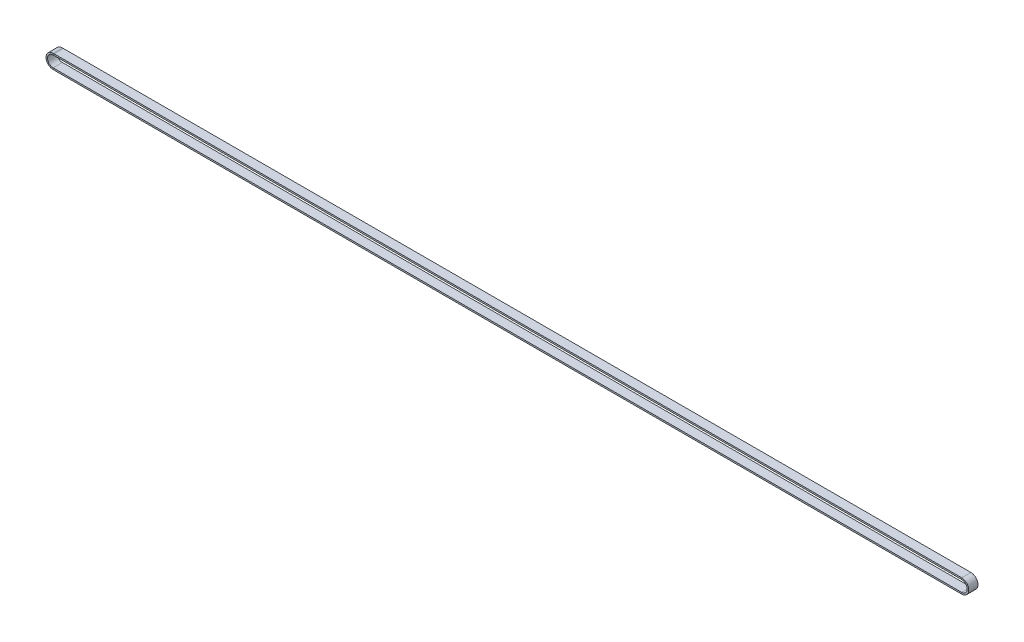
SolidWorks part; units mm, degrees
ref_plane "Front Plane" through (0, 0, 0) normal (0, 0, 1) x (1, 0, 0)
ref_plane "Top Plane" through (0, 0, 0) normal (0, 1, 0) x (1, 0, 0)
ref_plane "Right Plane" through (0, 0, 0) normal (1, 0, 0) x (0, 0, -1)
sketch "Sketch2" plane through (0, 0, -26.2334) normal (0, 0, 1) x (1, 0, 0)
  line L0 (0, 0) -> (1, 0) construction
  line L1 (0, 0) -> (0, 1) construction
  line L2 (-1, -57.8902) -> (883.5206, -57.8902)
  line L3 (883.5206, -71.6902) -> (-1, -71.6902)
  arc A0 (-1, -71.6902) -> (-1, -57.8902) centre (-1, -64.7902) cw
  arc A1 (883.5206, -57.8902) -> (883.5206, -71.6902) centre (883.5206, -64.7902) cw
sketch "Sketch3" plane through (0, 0, 0) normal (1, 0, 0) x (0, 0, -1)
  line L1 (26.2334, -59.3902) -> (17.2334, -59.3902)
  line L2 (26.2334, -59.3902) -> (26.2334, -57.8902)
  line L3 (26.2334, -57.8902) -> (17.2334, -57.8902)
  line L4 (17.2334, -59.3902) -> (17.2334, -57.8902)
  dimension "D1" = 9
  dimension "D2" = 1.5
sweep "Sweep1" add profiles "Sketch3" path "Sketch2"
